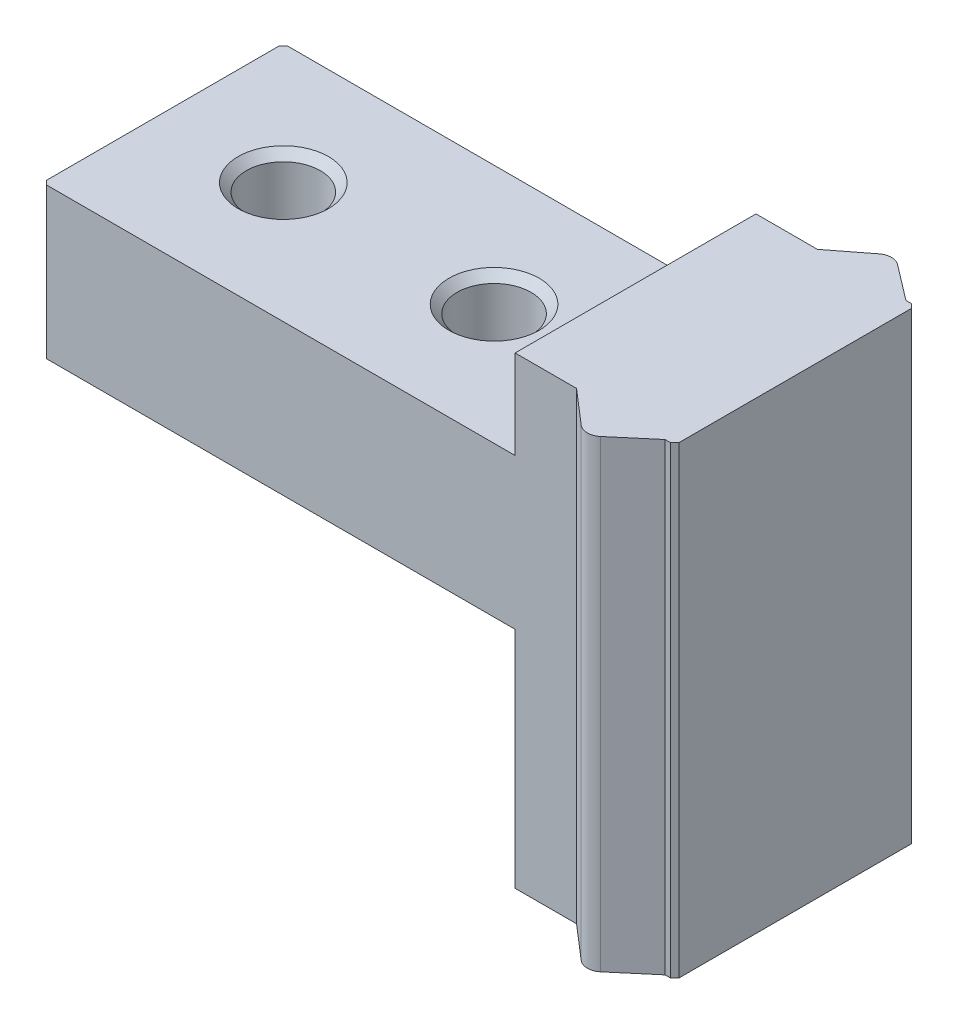
SolidWorks part; units mm, degrees
ref_plane "前视基准面" through (0, 0, 0) normal (0, 0, 1) x (1, 0, 0)
ref_plane "上视基准面" through (0, 0, 0) normal (0, 1, 0) x (1, 0, 0)
ref_plane "右视基准面" through (0, 0, 0) normal (1, 0, 0) x (0, 0, -1)
ref_plane "Plane1" through (0, 3, 0) normal (0, 1, 0) x (1, 0, 0)
sketch "Sketch1" plane through (0, 3, 0) normal (0, 1, 0) x (1, 0, 0)
  line L0 (-51.8, -4) -> (-49.76, -4)
  line L1 (-49.76, -4) -> (-48.6268, -4.9785)
  line L2 (-47.9765, -4.9813) -> (-46.82, -4)
  line L3 (-46.82, -4) -> (-46.6414, -4)
  line L4 (-46.6414, -4) -> (-46.5, -3.8586)
  line L5 (-46.5, -3.8586) -> (-46.5, 3.8586)
  line L6 (-46.5, 3.8586) -> (-46.6414, 4)
  line L7 (-46.6414, 4) -> (-46.82, 4)
  line L8 (-46.82, 4) -> (-47.9968, 4.8976)
  line L9 (-48.6065, 4.895) -> (-49.76, 4)
  line L10 (-49.76, 4) -> (-51.8, 4)
  line L11 (-51.8, 4) -> (-51.8, -4)
  arc A0 (-48.6268, -4.9785) -> (-47.9765, -4.9813) centre (-48.3, -4.6) ccw
  arc A1 (-47.9968, 4.8976) -> (-48.6065, 4.895) centre (-48.3, 4.5) ccw
extrude "Boss-Extrude1" add sketch "Sketch1" along normal blind 15.4
ref_plane "Plane2" through (0, 10.45, 0) normal (0, 1, 0) x (1, 0, 0)
sketch "Sketch2" plane through (0, 10.45, 0) normal (0, 1, 0) x (1, 0, 0)
  line L0 (-67.5, 3.8586) -> (-67.5, -3.8586)
  line L1 (-67.5, -3.8586) -> (-67.3586, -4)
  line L2 (-67.3586, -4) -> (-51.8, -4)
  line L3 (-51.8, -4) -> (-51.8, 4)
  line L4 (-51.8, 4) -> (-67.3586, 4)
  line L5 (-67.3586, 4) -> (-67.5, 3.8586)
extrude "Boss-Extrude2" add sketch "Sketch2" along normal blind 5
ref_plane "Plane3" through (0, 3.75, 0) normal (0, 1, 0) x (1, 0, 0)
ref_plane "Plane4" through (0, 9.55, 0) normal (0, 1, 0) x (1, 0, 0)
ref_plane "Plane5" through (0, 6.8, 0) normal (0, 1, 0) x (1, 0, 0)
ref_plane "Plane6" through (0, 14.8, 0) normal (0, 1, 0) x (1, 0, 0)
sketch "Sketch3" plane through (0, 0, 0) normal (0, 0, 1) x (1, 0, 0)
  line L0 (-63.5, 10.44) -> (-65, 10.44)
  line L1 (-65, 10.44) -> (-64.7295, 10.7105)
  line L2 (-64.7295, 10.7105) -> (-64.7295, 15.1795)
  line L3 (-64.7295, 15.1795) -> (-65, 15.45)
  line L4 (-65, 15.45) -> (-63.5, 15.45)
  line L5 (-63.5, 15.45) -> (-63.5, 10.44)
  line L6 (-63.5, 15.45) -> (-63.5, 10.44) construction
revolve "Cut-Revolve1" cut sketch "Sketch3" angle 360 about L6 reverse direction yes
cosmetic thread "Cosmetic Thread1" parameters "D1"=5, "D2"=6.836
sketch "Sketch4" plane through (0, 0, 0) normal (0, 0, 1) x (1, 0, 0)
  line L0 (-56.5, 10.44) -> (-58, 10.44)
  line L1 (-58, 10.44) -> (-57.7295, 10.7105)
  line L2 (-57.7295, 10.7105) -> (-57.7295, 15.1795)
  line L3 (-57.7295, 15.1795) -> (-58, 15.45)
  line L4 (-58, 15.45) -> (-56.5, 15.45)
  line L5 (-56.5, 15.45) -> (-56.5, 10.44)
  line L6 (-56.5, 15.45) -> (-56.5, 10.44) construction
revolve "Cut-Revolve2" cut sketch "Sketch4" angle 360 about L6 reverse direction yes
cosmetic thread "Cosmetic Thread2" parameters "D1"=5, "D2"=6.836
ref_plane "Plane7" through (0, 12.95, 0) normal (0, 1, 0) x (1, 0, 0)
ref_plane "for body XY" through (0, 0, 0) normal (0, -1, 0) x (-1, 0, 0)
ref_plane "for body XZ" through (0, 0, 0) normal (0, 0, -1) x (-1, 0, 0)
ref_plane "for body YZ" through (-48.3, 0, 0) normal (1, 0, 0) x (0, 0, -1)
ref_axis "for body X" through (-80.9, 0, 0) along (1, 0, 0)
ref_axis "for body Y" through (-48.3, 0, -50) along (0, 0, 1)
ref_axis "for body Z" through (-48.3, -50, 0) along (0, 1, 0)
sketch3d "for body"
  point P0 (-48.3, 0, 0)
scale "缩放比例1" bodies to scale 105 scale about centroid uniform scaling yes scale factor 2.5
equation "\"Dummy1\"= \"图号代码\""
equation "\"Dummy2\"= \"名称代码\""
